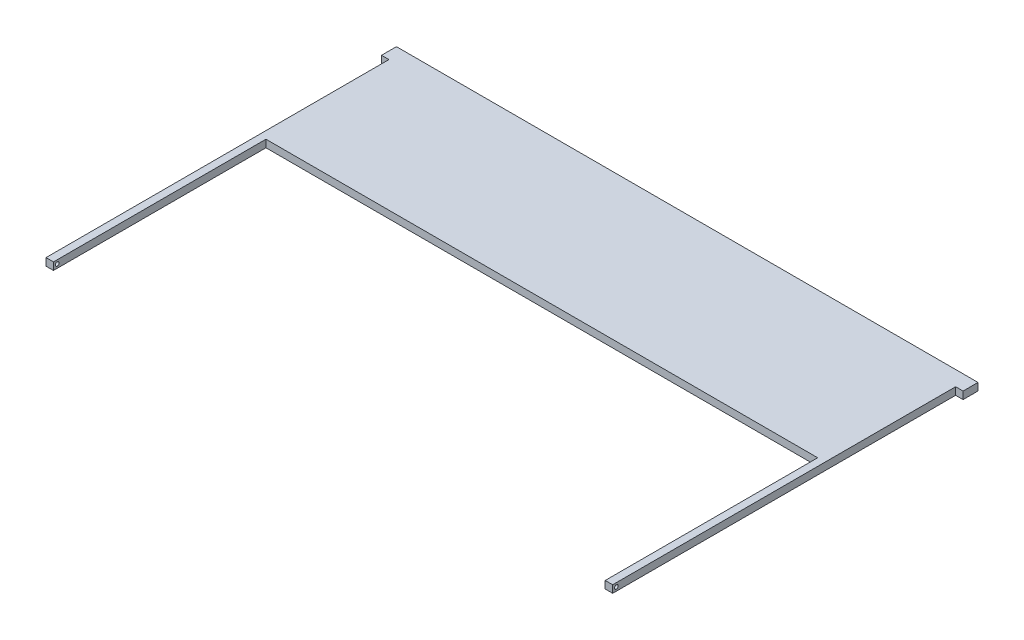
SolidWorks part; units mm, degrees
other "Markup1"
sketch "Sketch12" plane through (250.825, 22.225, 158.75) normal (0.1153, 0.0728, 0.9907) x (0.9687, -0.2289, -0.0959)
material "6061 Alloy"
ref_plane "Front Plane" through (0, 0, 0) normal (0, 0, 1) x (1, 0, 0)
ref_plane "Top Plane" through (0, 0, 0) normal (0, 1, 0) x (1, 0, 0)
ref_plane "Right Plane" through (0, 0, 0) normal (1, 0, 0) x (0, 0, -1)
sketch "Sketch1" plane through (0, 0, 0) normal (0, 1, 0) x (1, 0, 0)
  line L1 (-241.3, 152.4) -> (241.3, 152.4)
  line L2 (-241.3, 152.4) -> (-241.3, -152.4)
  line L3 (-241.3, -152.4) -> (241.3, -152.4)
  line L4 (241.3, 152.4) -> (241.3, -152.4)
  line L5 (-241.3, 152.4) -> (241.3, -152.4) construction
  line L6 (-241.3, -152.4) -> (241.3, 152.4) construction
  point P0 (0, 0)
  dimension "D1" = 482.6
  dimension "D2" = 304.8
extrude "Boss-Extrude1" add sketch "Sketch1" along normal blind 12.7
sketch "Sketch2" plane through (0, 12.7, 0) normal (0, 1, 0) x (1, 0, 0)
  line L0 (-241.3, -152.4) -> (241.3, -152.4) construction
  line L1 (-241.3, 152.4) -> (-234.95, 152.4)
  line L2 (-241.3, 152.4) -> (-241.3, -152.4)
  line L3 (-241.3, -152.4) -> (-234.95, -152.4)
  line L4 (-234.95, 28.575) -> (-234.95, -152.4)
  line L5 (241.3, 152.4) -> (-241.3, 152.4) construction
  line L6 (241.3, 152.4) -> (234.95, 152.4)
  line L7 (241.3, 152.4) -> (241.3, -152.4)
  line L8 (241.3, -152.4) -> (234.95, -152.4)
  line L9 (234.95, 28.575) -> (234.95, -152.4)
  line L10 (-234.95, 152.4) -> (234.95, 152.4)
  line L12 (-234.95, 28.575) -> (234.95, 28.575)
  point P14 (-238.125, -152.4)
  dimension "D1" = 6.35
  dimension "D2" = 180.975
extrude "Boss-Extrude2" add sketch "Sketch2" along normal blind 6.35
sketch "Sketch3" plane through (-241.3, 0, 0) normal (-1, 0, 0) x (0, 0, 1)
  line L0 (152.4, 19.05) -> (152.4, 0) construction
  line L1 (-152.4, 19.05) -> (152.4, 19.05) construction
  circle A0 centre (149.225, 15.875) radius 1.5875
  dimension "D3" = 3.175
  dimension "D1" = 3.175
  dimension "D2" = 3.175
extrude "Cut-Extrude1" cut sketch "Sketch3" against normal through all
sketch "Sketch4" plane through (0, 0, 152.4) normal (0, 0, 1) x (1, 0, 0)
  line L0 (-241.3, 19.05) -> (-241.3, 0) construction
  line L1 (-241.3, 12.7) -> (-247.65, 12.7)
  line L2 (-241.3, 12.7) -> (-241.3, 0)
  line L3 (-241.3, 0) -> (-247.65, 0)
  line L4 (-247.65, 12.7) -> (-247.65, 0)
  line L5 (-241.3, 0) -> (241.3, 0) construction
  dimension "D1" = 12.7
  dimension "D2" = 6.35
extrude "Boss-Extrude3" add sketch "Sketch4" against normal blind 292.1
sketch "Sketch5" plane through (-241.3, 0, 0) normal (-1, 0, 0) x (0, 0, 1)
  line L0 (-152.4, 0) -> (-139.7, 0) construction
  line L1 (-152.4, 19.05) -> (-139.7, 19.05)
  line L2 (-152.4, 19.05) -> (-152.4, 0)
  line L3 (-152.4, 0) -> (-139.7, 0)
  line L4 (-139.7, 19.05) -> (-139.7, 0)
  line L5 (-139.7, 0) -> (-139.7, 12.7) construction
extrude "Boss-Extrude4" add sketch "Sketch5" along normal up to surface (6.35 mm away) up to face at (-247.65, 6.35, 6.35)
mirror "Mirror1" about plane through (0, 0, 0) normal (1, 0, 0) of "Boss-Extrude4", "Boss-Extrude3"
sketch "Sketch6" plane through (-241.3, 0, 0) normal (-1, 0, 0) x (0, 0, 1)
  line L0 (147.32, 6.35) -> (128.27, 6.35) construction
  line L1 (147.32, 2.54) -> (128.27, 2.54)
  line L2 (147.32, 10.16) -> (128.27, 10.16)
  line L3 (152.4, 19.05) -> (152.4, 12.7) construction
  line L5 (152.4, 12.7) -> (152.4, 0) construction
  arc A0 (147.32, 2.54) -> (147.32, 10.16) centre (147.32, 6.35) ccw
  arc A1 (128.27, 10.16) -> (128.27, 2.54) centre (128.27, 6.35) ccw
  point P2 (137.795, 6.35)
  point P11 (152.4, 6.35)
  dimension "D1" = 19.05
  dimension "D2" = 5.08
  dimension "D3" = 7.62
extrude "Cut-Extrude2" cut sketch "Sketch6" against normal blind 25.4 from surface starting at face at (-247.65, 10.5833, -46.5667)
extrude "Cut-Extrude3" cut sketch "Sketch6<2>" along normal blind 25.4 from surface starting at face at (247.65, 10.5833, -46.5667)
sketch "Sketch6<2>" plane through (-241.3, 0, 0) normal (-1, 0, 0) x (0, 0, 1) same geometry as "Sketch6"
sketch "Sketch11" plane through (0, 0, 0) normal (0, -1, 0) x (1, 0, 0)
  line L0 (-247.65, 124.46) -> (-222.25, 124.46)
  line L1 (-222.25, 124.46) -> (-222.25, 140.97)
  line L2 (-222.25, 140.97) -> (-247.65, 124.46)
  line L3 (-222.25, 128.27) -> (-222.25, 147.32) construction
  dimension "D1" = 10.16
extrude "Boss-Extrude5" add sketch "Sketch11" against normal up to surface (10.16 mm away) from surface up to face at (-234.95, 10.16, 137.795) starting at face at (-234.95, 2.54, 137.795)
mirror "Mirror2" about plane through (0, 0, 0) normal (1, 0, 0) of "Boss-Extrude5"
ref_plane "Plane1" through (247.65, 19.05, -152.4) normal (-1, 0, 0) x (0, 0, 1)
sketch "Sketch13" plane through (247.65, 19.05, -152.4) normal (-1, 0, 0) x (0, 0, 1)
  line L0 (0, 0) -> (0, -19.05) construction
  line L1 (304.8, -19.05) -> (0, -19.05)
  line L2 (304.8, -19.05) -> (304.8, -6.35)
  line L3 (304.8, -6.35) -> (0, -6.35)
  line L4 (0, -19.05) -> (0, -6.35)
  line L5 (12.7, -6.35) -> (304.8, -6.35) construction
extrude "Cut-Extrude5" cut sketch "Sketch13" against normal through all and the other way through all
sketch "Sketch14" plane through (0, 19.05, 0) normal (0, 1, 0) x (1, 0, 0)
  line L0 (-95.25, 152.4) -> (-95.25, 28.575)
  line L1 (247.65, 152.4) -> (-247.65, 152.4) construction
  line L2 (-234.95, 28.575) -> (234.95, 28.575) construction
  line L3 (95.25, 28.575) -> (95.25, 152.4)
  line L4 (-247.65, 139.7) -> (-247.65, 152.4) construction
  line L5 (247.65, 139.7) -> (247.65, 152.4) construction
  dimension "D1" = 152.4
  dimension "D2" = 152.4
